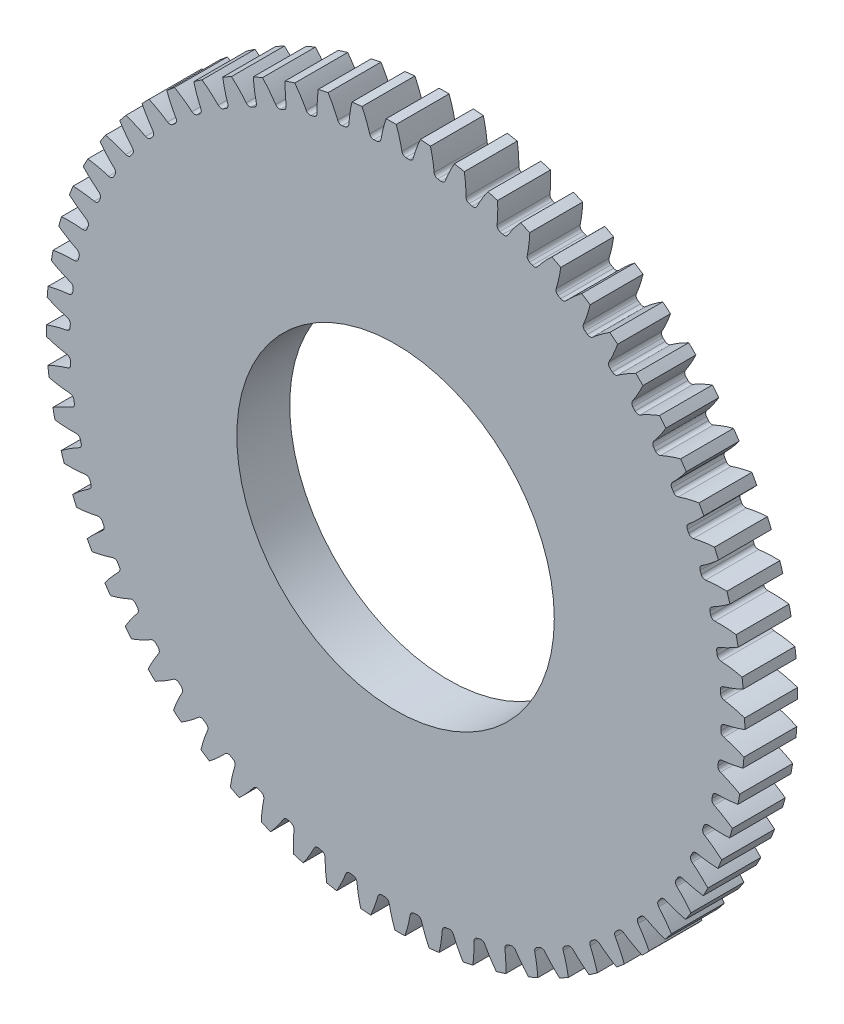
SolidWorks part; units mm, degrees
ref_plane "Front" through (0, 0, 0) normal (0, 0, 1) x (1, 0, 0)
ref_plane "Top" through (0, 0, 0) normal (0, 1, 0) x (1, 0, 0)
ref_plane "Right" through (0, 0, 0) normal (1, 0, 0) x (0, 0, -1)
sketch "Sketch3" plane through (0, 0, 0) normal (0, 0, 1) x (1, 0, 0)
  circle A0 centre (0, 0) radius 41.91
  dimension "od" = 83.82
extrude "gearBody" add sketch "Sketch3" along normal blind 6.35
sketch "Sketch2" plane through (0, 0, 0) normal (0, 0, 1) x (1, 0, 0)
  line L0 (0, 0) -> (36.3505, 15.0569) construction
  line L1 (49.1027, -9.5876) -> (0, 0) construction
  line L2 (0, 0) -> (36.3143, 0) construction
  line L3 (40.6371, -0.4885) -> (40.564, -2.485) construction
  line L5 (40.6005, -1.4868) -> (0, 0) construction
  line L7 (0, 0) -> (39.3455, 0) construction
  arc A0 (39.3376, -0.7896) -> (39.29, -2.0897) centre (0, 0) ccw construction
  arc A1 (41.9099, -0.0801) -> (41.8035, -2.9854) centre (0, 0) ccw construction
  arc A2 (40.6371, -0.4885) -> (40.564, -2.485) centre (0, 0) ccw construction
  arc A3 (39.0317, -1.6169) -> (39.0454, -1.2423) centre (0, 0) ccw
  arc A4 (49.1027, -9.5876) -> (39.399, -2.119) centre (35.1519, -17.6753) ccw
  arc A5 (49.1027, -9.5876) -> (49.6724, 5.9705) centre (0, 0) ccw
  arc A6 (49.6724, 5.9705) -> (39.4484, -0.7683) centre (36.3505, 15.0569) cw
  arc A7 (39.0454, -1.2423) -> (39.4484, -0.7683) centre (39.5443, -1.2582) cw
  arc A8 (39.399, -2.119) -> (39.0317, -1.6169) centre (39.5304, -1.6375) cw
  point P6 (49.6724, 5.9705)
  point P22 (49.1027, -9.5876)
  dimension "baseDia" = 78.691
  dimension "od" = 83.82
  dimension "pd" = 81.28
  dimension "rd" = 78.1304
  dimension "rFillet" = 0.4991
  dimension "pointX" = 49.6724
  dimension "pointY" = 5.9705
  dimension "CTT" = 1.9964
  dimension "flankCenterAngle" = 22.5
extrude "toothCut" cut sketch "Sketch2" along normal through all
pattern_circular "CirPattern1" count 64 over 360 about axis through (0, 0, 6.35) along (0, 0, -1) of "toothCut"
sketch "hub1Dia" plane through (0, 0, 0) normal (0, 0, -1) x (-1, 0, 0)
  circle A0 centre (0, 0) radius 25.4
  dimension "hub1Dia" = 50.8
extrude "hub1" [suppressed] add sketch "hub1Dia" along normal blind 19.05
sketch "hub2Dia" plane through (0, 0, 6.35) normal (0, 0, 1) x (1, 0, 0)
  circle A0 centre (0, 0) radius 21.844
  dimension "hub2dia" = 43.688
extrude "hub2" [suppressed] add sketch "hub2Dia" along normal blind 16.002
sketch "boreDia" plane through (0, 0, 0) normal (0, 0, 1) x (1, 0, 0)
  circle A0 centre (0, 0) radius 19.05
  dimension "boreDia" = 38.1
extrude "bore" cut sketch "boreDia" against normal mid plane 25.4
chamfer "hub2Chamfer" [suppressed] distance 0.508 angle 45
chamfer "hub2BoreChamfer" [suppressed] distance 0.508 angle 45
chamfer "hub1BoreChamfer" [suppressed] distance 0.508 angle 45
chamfer "hub1Chamfer" [suppressed] distance 0.508 angle 45
chamfer "BoreChamfer2" [suppressed] distance 0.508 angle 45
chamfer "boreChamfer1" [suppressed] distance 0.508 angle 45
